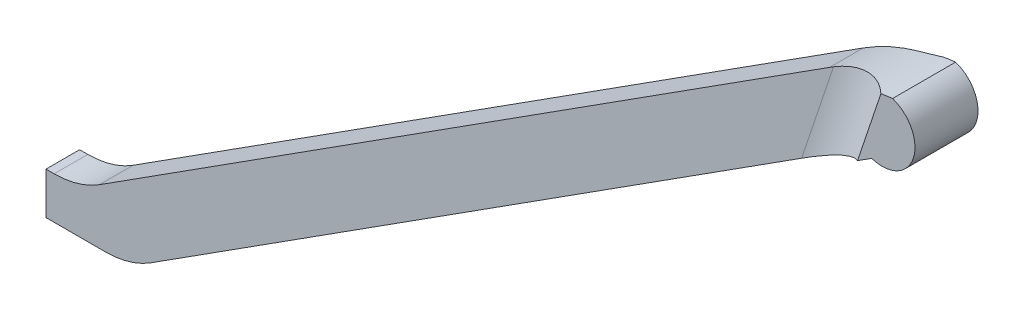
SolidWorks part; units mm, degrees
material "PBT General Purpose"
ref_plane "Front Plane" through (0, 0, 0) normal (0, 0, 1) x (1, 0, 0)
ref_plane "Top Plane" through (0, 0, 0) normal (0, 1, 0) x (1, 0, 0)
ref_plane "Right Plane" through (0, 0, 0) normal (1, 0, 0) x (0, 0, -1)
sketch "Sketch1" plane through (0, 0, 0) normal (0, 0, 1) x (1, 0, 0)
  line L0 (0, 0) -> (2, 0)
  line L1 (2, 0) -> (20.2947, 11.6932)
  line L5 (21.0543, 13.9589) -> (0.7793, 1)
  line L6 (0.7793, 1) -> (0, 1)
  line L7 (0, 1) -> (0, 0)
  line L8 (20.2947, 11.6932) -> (21.0543, 13.9589)
  dimension "D2" = 1
  dimension "D4" = 1.5
  dimension "D5" = 2
extrude "Boss-Extrude1" add sketch "Sketch1" along normal mid plane 0.8
sketch "Sketch2" plane through (0, 0, 0.4) normal (0, 0, 1) x (1, 0, 0)
  line L0 (21.0543, 13.9589) -> (20.7172, 13.7435)
  line L1 (21.0543, 13.9589) -> (0.7793, 1) construction
  line L2 (20.7172, 13.7435) -> (19.9576, 11.4778)
  line L3 (2, 0) -> (20.2947, 11.6932) construction
  line L4 (19.9576, 11.4778) -> (20.2947, 11.6932)
  line L5 (20.2947, 11.6932) -> (21.0543, 13.9589)
  dimension "D1" = 0.4
extrude "Boss-Extrude2" add sketch "Sketch2" along normal mid plane 1.5 from offset 0.1 offset against normal yes
fillet "Fillet1" radius 2 2 edges at (2, 0, 0) (0.7793, 1, 0)
fillet "Fillet2" radius 2 2 edges at (20.3374, 12.6106, -0.4) (20.3374, 12.6106, 0.4)
sketch "Sketch4" plane through (0, 0, 0.4) normal (0, 0, 1) x (1, 0, 0)
  line L0 (17.6126, 13.0112) -> (21.9762, 13.2358)
  line L1 (21.9762, 14.5201) -> (17.6126, 14.2325)
  line L2 (17.6126, 14.2325) -> (17.6126, 13.0112)
  line L3 (21.9762, 14.5201) -> (21.9762, 13.2358)
extrude "Cut-Extrude1" cut sketch "Sketch4" against normal through all both and the other way through all
fillet "Fillet3" radius 5 1 edges at (19.7432, 13.1209, 0.073)
sketch "Sketch5" plane through (0, 0, 1.05) normal (0, 0, 1) x (1, 0, 0)
  line L0 (20.2947, 11.6932) -> (20.7914, 13.1748) construction
  line L1 (20.7914, 13.1748) -> (20.2947, 11.6932)
  arc A0 (20.7914, 13.1748) -> (20.2947, 11.6932) centre (20.5431, 12.434) cw
extrude "Boss-Extrude4" add sketch "Sketch5" against normal blind 1.5
